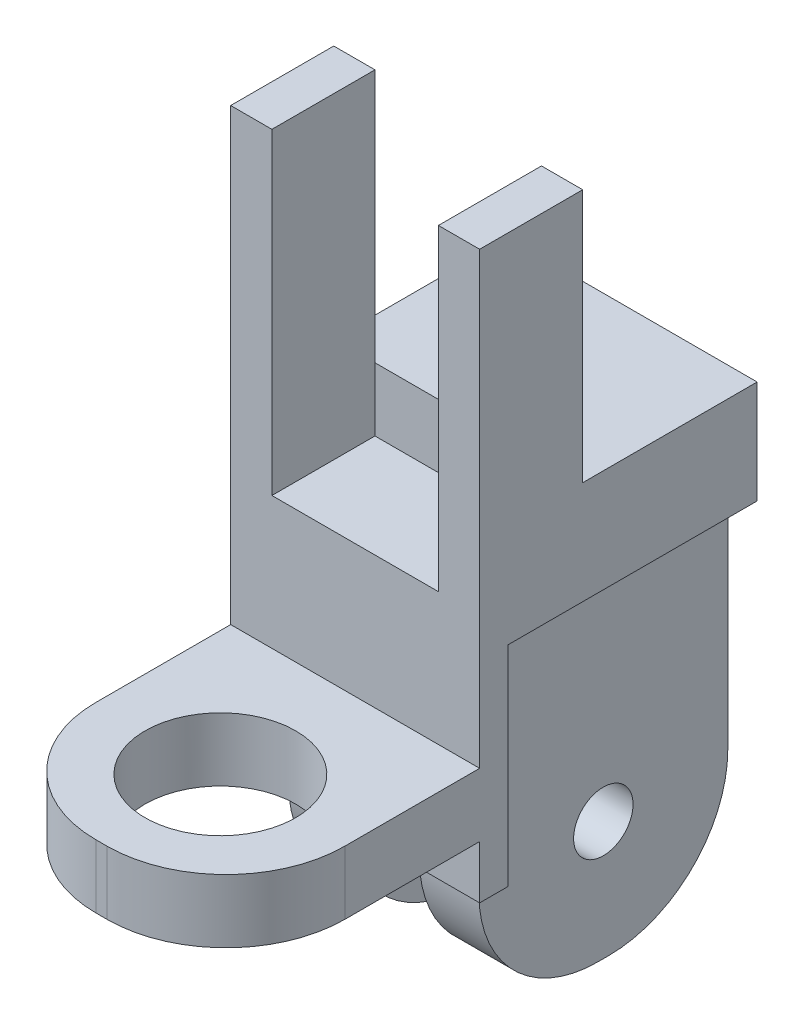
SolidWorks part; units mm, degrees
ref_plane "Front Plane" through (0, 0, 0) normal (0, 0, 1) x (1, 0, 0)
ref_plane "Top Plane" through (0, 0, 0) normal (0, 1, 0) x (1, 0, 0)
ref_plane "Right Plane" through (0, 0, 0) normal (1, 0, 0) x (0, 0, -1)
sketch "Sketch4" plane through (0, 0, 0) normal (0, 0, 1) x (1, 0, 0)
  line L0 (0, 82.063) -> (0, -112.4411) construction
  line L1 (-144.2959, 0) -> (145.5617, 0) construction
  line L2 (-12.7, 12.7) -> (-12.7, -12.7)
  line L3 (-15.7, 15.7) -> (15.7, 15.7)
  line L4 (-15.7, 15.7) -> (-15.7, -15.7)
  line L5 (-15.7, -15.7) -> (15.7, -15.7)
  line L6 (15.7, 15.7) -> (15.7, -15.7)
  line L7 (-12.7, -12.7) -> (12.7, -12.7)
  line L8 (12.7, 12.7) -> (12.7, -12.7)
  line L9 (-12.7, 12.7) -> (12.7, 12.7)
  dimension "D2" = 12.7
  dimension "D3" = 12.7
  dimension "D4" = 12.7
  dimension "D5" = 12.7
  dimension "D1" = 3
extrude "Boss-Extrude3" add sketch "Sketch4" along normal blind 30
sketch "Sketch5" plane through (0, 0, 30) normal (0, 0, 1) x (1, 0, 0)
  line L0 (-15.7, 15.7) -> (15.7, 15.7)
  line L1 (15.7, 15.7) -> (15.7, -15.7)
  line L2 (15.7, -15.7) -> (-15.7, -15.7)
  line L3 (-15.7, -15.7) -> (-15.7, 15.7)
extrude "Boss-Extrude4" add sketch "Sketch5" along normal blind 5
sketch "Sketch6" plane through (0, 0, 35) normal (0, 0, 1) x (1, 0, 0)
  line L0 (-14.6567, 0) -> (15.7, 0) construction
  line L1 (15.7, -15.7) -> (15.7, 15.7) construction
  line L2 (-15.7, 4) -> (15.7, 4)
  line L3 (-15.7, 15.7) -> (-15.7, -15.7) construction
  line L4 (15.7, 4) -> (15.7, -4)
  line L5 (15.7, -4) -> (-15.7, -4)
  line L6 (-15.7, -4) -> (-15.7, 4)
  dimension "D1" = 4
  dimension "D2" = 4
extrude "Boss-Extrude5" add sketch "Sketch6" along normal blind 5
sketch "Sketch7" plane through (0, -4, 0) normal (0, -1, 0) x (1, 0, 0)
  line L0 (-15.7, 40) -> (-15.7, 52)
  line L1 (-0.7, 67) -> (0.7, 67)
  line L2 (15.7, 52) -> (15.7, 40)
  line L3 (-15.7, 40) -> (15.7, 40) construction
  line L4 (15.7, 40) -> (-15.7, 40)
  line L5 (0, 0) -> (0, 92.3619) construction
  arc A0 (0.7, 67) -> (15.7, 52) centre (0.7, 52) cw
  arc A1 (-15.7, 52) -> (-0.7, 67) centre (-0.7, 52) cw
  point P9 (15.7, 67)
  point P12 (-15.7, 67)
  dimension "D3" = 15
  dimension "D1" = 27
  dimension "D2" = 31.4
extrude "Boss-Extrude6" add sketch "Sketch7" against normal blind 8
sketch "Sketch8" plane through (0, -4, 0) normal (0, -1, 0) x (1, 0, 0)
  line L0 (0, 67.4318) -> (0, -5.9603) construction
  line L1 (0.7, 67) -> (-0.7, 67) construction
  circle A0 centre (0, 52) radius 9.5
  dimension "D1" = 15
extrude "Boss-Extrude7" add sketch "Sketch8" along normal blind 8
mirror "Mirror1" about plane through (0, 0, 0) normal (0, 1, 0) of "Boss-Extrude7"
sketch "Sketch9" plane through (0, 15.7, 0) normal (0, 1, 0) x (1, 0, 0)
  line L1 (-15.7, -32) -> (15.7, -32)
  line L2 (-15.7, -35) -> (-15.7, 0) construction
  line L3 (15.7, -35) -> (15.7, 0) construction
  line L4 (0, 15.8647) -> (0, -78.6922) construction
  line L5 (0, -52) -> (31.7707, -52) construction
  line L6 (31.7707, -52) -> (-30.9902, -52) construction
  line L7 (-15.7, -32) -> (-15.7, -22)
  line L8 (-15.7, -22) -> (15.7, -22)
  line L9 (15.7, -22) -> (15.7, -32)
  dimension "D1" = 20
  dimension "D2" = 10
extrude "Boss-Extrude8" add sketch "Sketch9" along normal blind 5
sketch "Sketch10" plane through (0, 15.7, 0) normal (0, 1, 0) x (1, 0, 0)
  line L0 (-15.7, -22) -> (-15.7, -12)
  line L1 (-15.7, -22) -> (-15.7, 0) construction
  line L2 (-15.7, -12) -> (15.7, -12)
  line L3 (15.7, -22) -> (15.7, 0) construction
  line L4 (15.7, -12) -> (15.7, -22)
  line L5 (15.7, -22) -> (-15.7, -22)
  dimension "D1" = 10
extrude "Boss-Extrude9" add sketch "Sketch10" along normal blind 13
sketch "Sketch11" plane through (0, 20.7, 0) normal (0, 1, 0) x (1, 0, 0)
  line L0 (-15.7, -22) -> (-10.5, -22)
  line L1 (15.7, -22) -> (-15.7, -22) construction
  line L2 (-10.5, -22) -> (-10.5, -32)
  line L3 (-15.7, -32) -> (15.7, -32) construction
  line L4 (-10.5, -32) -> (-15.7, -32)
  line L5 (-15.7, -32) -> (-15.7, -22)
  line L6 (10.5, -22) -> (10.5, -32)
  line L7 (-15.7, -22) -> (15.7, -22) construction
  line L8 (-15.7, -32) -> (15.7, -32) construction
  line L9 (10.5, -32) -> (15.7, -32)
  line L10 (15.7, -32) -> (15.7, -22)
  line L11 (15.7, -32) -> (15.7, -22) construction
  line L12 (15.7, -22) -> (10.5, -22)
  dimension "D1" = 5.2
  dimension "D2" = 5.2
extrude "Boss-Extrude10" add sketch "Sketch11" along normal blind 40
sketch "Sketch12" plane through (0, 0, 32) normal (0, 0, 1) x (1, 0, 0)
  line L0 (-15.7, 60.7) -> (-10.5, 60.7)
  line L1 (-10.5, 60.7) -> (-10.5, 20.7)
  line L2 (-10.5, 20.7) -> (10.5, 20.7)
  line L3 (10.5, 20.7) -> (10.5, 60.7)
  line L4 (10.5, 60.7) -> (15.7, 60.7)
  line L5 (15.7, 60.7) -> (15.7, 15.7)
  line L6 (15.7, 15.7) -> (-15.7, 15.7)
  line L7 (-15.7, 15.7) -> (-15.7, 60.7)
  dimension "D1" = 5.2
  dimension "D2" = 5.2
  dimension "D3" = 21
extrude "Boss-Extrude11" add sketch "Sketch12" along normal blind 3
sketch "Sketch13" plane through (-15.7, 0, 0) normal (-1, 0, 0) x (0, 0, 1)
  line L5 (0, 15.7) -> (31.4, 15.7)
  line L6 (31.4, 15.7) -> (31.4, -15.7)
  line L7 (35, -15.7) -> (0, -15.7) construction
  line L8 (31.4, -15.7) -> (0, -15.7)
  line L9 (0, -15.7) -> (0, 15.7)
  dimension "D1" = 31.4
extrude "Cut-Extrude1" cut sketch "Sketch13" against normal blind 31.4
sketch "Sketch15" plane through (0, 0, 12) normal (0, 0, -1) x (-1, 0, 0)
  line L0 (-15.7, 28.7) -> (15.7, 28.7)
  line L1 (15.7, 28.7) -> (15.7, 15.7)
  line L2 (15.7, 15.7) -> (-15.7, 15.7)
  line L3 (-15.7, 15.7) -> (-15.7, 28.7)
extrude "Boss-Extrude12" add sketch "Sketch15" along normal blind 12
sketch "Sketch17" plane through (0, 15.7, 0) normal (0, -1, 0) x (1, 0, 0)
  line L0 (0, 70.9174) -> (0, -6.6676) construction
  line L1 (-12, 31.4) -> (-12, 0)
  line L2 (15.7, 31.4) -> (-15.7, 31.4) construction
  line L3 (15.7, 0) -> (-15.7, 0) construction
  line L4 (-12, 0) -> (-4.5, 0)
  line L5 (-4.5, 0) -> (-4.5, 31.4)
  line L6 (15.7, 31.4) -> (-15.7, 31.4) construction
  line L7 (-4.5, 31.4) -> (-12, 31.4)
  line L8 (-15.7, 31.4) -> (-15.7, 0) construction
  dimension "D1" = 7.5
  dimension "D2" = 3.7
  dimension "D3" = 4.5
extrude "Boss-Extrude13" add sketch "Sketch17" along normal blind 10
sketch "Sketch18" plane through (-12, 0, 0) normal (-1, 0, 0) x (0, 0, 1)
  line L1 (31.4, 5.7) -> (0, 5.7)
  line L4 (0, 5.7) -> (0, -13.3)
  line L5 (15, -28.3) -> (16.4, -28.3)
  line L6 (31.4, -13.3) -> (31.4, 5.7)
  arc A3 (16.4, -28.3) -> (31.4, -13.3) centre (16.4, -13.3) ccw
  arc A4 (0, -13.3) -> (15, -28.3) centre (15, -13.3) ccw
  circle A5 centre (15.7, -13.3) radius 3.75
  point P12 (0, -28.3)
  dimension "D1" = 34
  dimension "D2" = 15
  dimension "D3" = 15
  dimension "D4" = 15.7
extrude "Boss-Extrude14" add sketch "Sketch18" against normal blind 7.5
mirror "Mirror3" about plane through (0, 0, 0) normal (1, 0, 0) of "Boss-Extrude13", "Boss-Extrude14"
sketch "Sketch19" plane through (15.7, 0, 0) normal (1, 0, 0) x (0, 0, -1)
  line L0 (-31.4, -10.7) -> (-35, -10.7)
  line L3 (-31.4, -15.7) -> (-31.4, 15.7) construction
  line L4 (-35, -15.7) -> (-35, -4) construction
  line L5 (-35, -10.7) -> (-35, -15.7)
  line L6 (-35, -15.7) -> (-31.4, -15.7)
  line L7 (-31.4, -15.7) -> (-31.4, -10.7)
  dimension "D1" = 5
extrude "Cut-Extrude2" cut sketch "Sketch19" against normal blind 31.4
extrude "Cut-Extrude3" cut sketch "Sketch8<2>" against normal blind 24 from offset 8
sketch "Sketch8<2>" plane through (0, -4, 0) normal (0, -1, 0) x (1, 0, 0) same geometry as "Sketch8"
sketch "Sketch20" plane through (0, -10.7, 0) normal (0, -1, 0) x (1, 0, 0)
  line L0 (-4.5, 31.4) -> (-4.5, 32.4)
  line L1 (-4.5, 32.4) -> (4.5, 32.4)
  line L2 (4.5, 32.4) -> (4.5, 31.4)
  line L3 (4.5, 31.4) -> (-4.5, 31.4)
  dimension "D1" = 1
extrude "Cut-Extrude4" cut sketch "Sketch20" against normal blind 26.4
